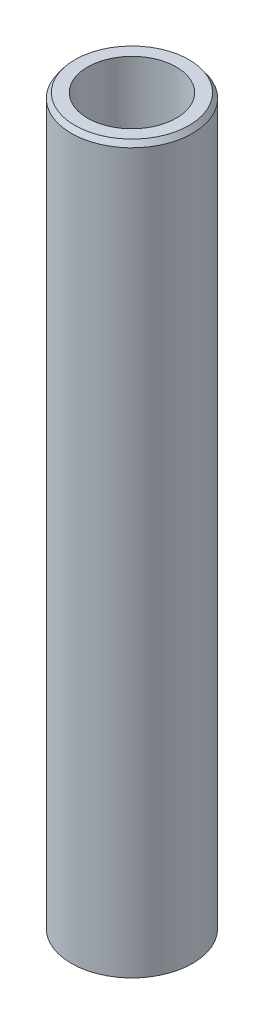
SolidWorks part; units mm, degrees
ref_plane "Front Plane" through (0, 0, 0) normal (0, 0, 1) x (1, 0, 0)
ref_plane "Top Plane" through (0, 0, 0) normal (0, 1, 0) x (1, 0, 0)
ref_plane "Right Plane" through (0, 0, 0) normal (1, 0, 0) x (0, 0, -1)
sketch "Sketch1" plane through (0, 0, 0) normal (0, 1, 0) x (1, 0, 0)
  circle A0 centre (0, 0) radius 50
  dimension "SHAFT_OD" = 100
extrude "Boss-Extrude1" add sketch "Sketch1" along normal blind 600
sketch "Sketch2" plane through (0, 0, 0) normal (0, 1, 0) x (1, 0, 0)
  circle A0 centre (0, 0) radius 36.5903
  dimension "BORE_D" = 73.1806
extrude "Cut-Extrude1" cut sketch "Sketch2" along normal through all
chamfer "Chamfer1" distance 4.1308 angle 35.663 2 edges at (0, 600, 50) (0, 0, 50) first distance on face at (0, 600, 50) first distance on face at (0, 0, 36.5903)
